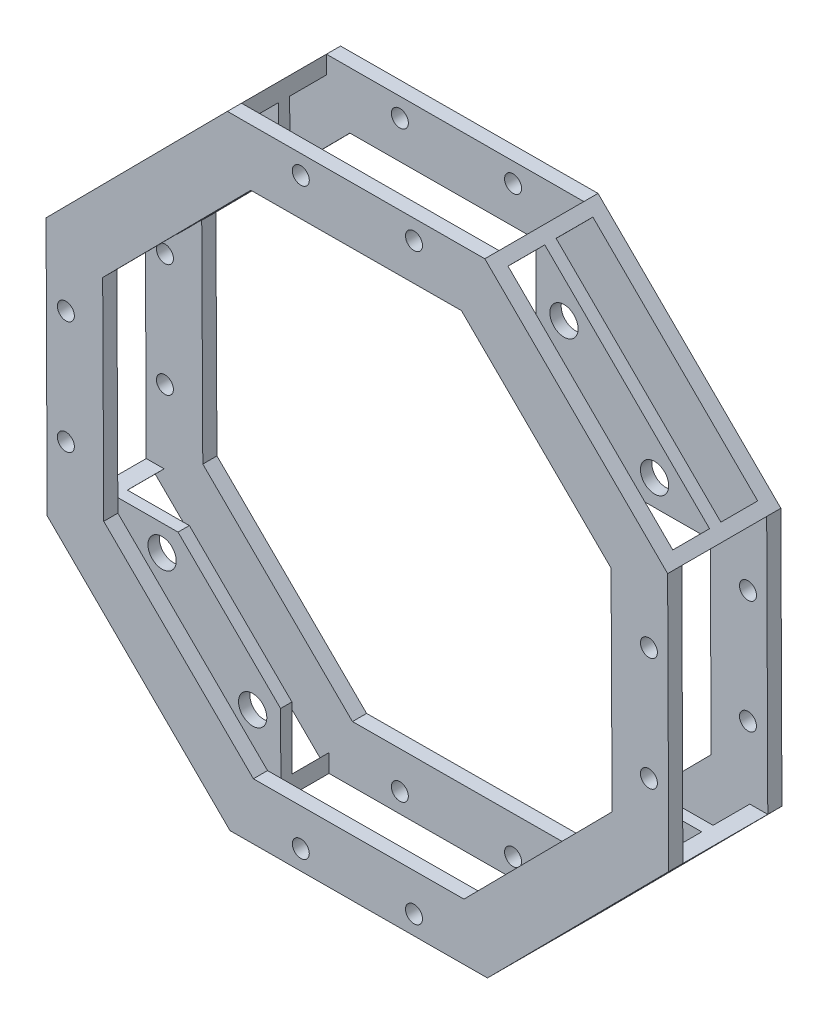
SolidWorks part; units mm, degrees
ref_plane "Plano frontal" through (0, 0, 0) normal (0, 0, 1) x (1, 0, 0)
ref_plane "Plano superior" through (0, 0, 0) normal (0, 1, 0) x (1, 0, 0)
ref_plane "Plano direito" through (0, 0, 0) normal (1, 0, 0) x (0, 0, -1)
sketch "Esboço1" plane through (0, 0, 0) normal (0, 0, 1) x (1, 0, 0)
  line L1 (109.614, 45.9495) -> (45.0177, 110)
  line L2 (45.0177, 110) -> (-45.9495, 109.614)
  line L3 (-45.9495, 109.614) -> (-110, 45.0177)
  line L4 (-110, 45.0177) -> (-109.614, -45.9495)
  line L5 (-109.614, -45.9495) -> (-45.0177, -110)
  line L6 (-45.0177, -110) -> (45.9495, -109.614)
  line L7 (45.9495, -109.614) -> (110, -45.0177)
  line L8 (110, -45.0177) -> (109.614, 45.9495)
  line L9 (89.6222, 37.657) -> (36.7449, 90)
  line L10 (36.7449, 90) -> (-37.657, 89.6222)
  line L11 (-37.657, 89.6222) -> (-90, 36.7449)
  line L12 (-90, 36.7449) -> (-89.6222, -37.657)
  line L13 (-89.6222, -37.657) -> (-36.7449, -90)
  line L14 (-36.7449, -90) -> (37.657, -89.6222)
  line L15 (37.657, -89.6222) -> (90, -36.7449)
  line L16 (90, -36.7449) -> (89.6222, 37.657)
  circle A0 centre (0, 0) radius 109.808 construction
  circle A1 centre (0, 0) radius 89.8123 construction
extrude "Ressalto-extrusão1" add sketch "Esboço1" along normal blind 40
sketch "Esboço2" plane through (109.807, 0.4659, 0) normal (1, 0.0042, 0) x (0, 0, -1)
  line L0 (-40, -45.484) -> (-40, 45.484) construction
  line L2 (0, 0) -> (0, -30)
  line L3 (0, -30) -> (-40, -30)
  line L4 (-40, 0) -> (-40, -30)
  line L5 (-40, -45.484) -> (0, -45.484) construction
  line L7 (0, 0) -> (0, -30)
  line L8 (0, -30) -> (-40, -30)
  line L9 (-40, 0) -> (-40, -30)
  line L10 (0, 45.484) -> (-5, 45.484)
  line L11 (0, 45.484) -> (0, -30)
  line L12 (0, -30) -> (-5, -30)
  line L13 (-5, 45.484) -> (-5, -30)
  line L14 (-40, 45.484) -> (-35, 45.484)
  line L15 (-40, 45.484) -> (-40, -30)
  line L16 (-40, -30) -> (-35, -30)
  line L17 (-35, 45.484) -> (-35, -30)
  line L18 (-5, -30) -> (-35, -30)
  line L19 (-5, -30) -> (-5, -45.484)
  line L20 (-5, -45.484) -> (-35, -45.484)
  line L21 (-35, -30) -> (-35, -45.484)
  point P23 (-3.1004, -30)
  line M2 (0, 45.484) -> (-40, 45.484)
  line M4 (-40, -45.484) -> (0, -45.484)
extrude "Corte-extrusão1" cut sketch "Esboço2" against normal through all both and the other way through all contours L17 L3 L13 M2 | L8 L21 L19 M4 region at (109.9672, -37.2757, 20) region at (109.7742, 8.2078, 20)
sketch "Esboço3" plane through (-0.4659, 109.807, 0) normal (-0.0042, 1, 0) x (1, 0.0042, 0)
  line L0 (45.484, -40) -> (-45.484, -40) construction
  line L1 (0, 0) -> (30, 0)
  line L3 (0, -40) -> (30, -40)
  line L4 (30, 0) -> (30, -40)
  line L5 (45.484, -40) -> (45.484, 0) construction
  line L6 (0, 0) -> (30.0922, 0)
  line L8 (0, -40) -> (30.0922, -40)
  line L9 (30.0922, 0) -> (30.0922, -5)
  line L10 (-45.484, 0) -> (30.0922, 0)
  line L11 (-45.484, 0) -> (-45.484, -5)
  line L12 (-45.484, -5) -> (30.0922, -5)
  line L13 (30.0922, 0) -> (30.0922, -5)
  line L14 (-45.484, -40) -> (30.0922, -40)
  line L15 (-45.484, -40) -> (-45.484, -35)
  line L16 (-45.484, -35) -> (30.0922, -35)
  line L17 (30.0922, -40) -> (30.0922, -35)
  line L18 (30, -35) -> (45.484, -35)
  line L19 (30, -35) -> (30, -5)
  line L20 (30, -5) -> (45.484, -5)
  line L21 (45.484, -35) -> (45.484, -5)
  line L22 (30.0922, -35) -> (30.0922, -40)
  line M2 (-45.484, 0) -> (-45.484, -40)
  line M4 (45.484, -40) -> (45.484, 0)
extrude "Corte-extrusão2" cut sketch "Esboço3" against normal through all both and the other way through all contours L20 L4 L18 M4 | L16 L9 L12 M2 region at (37.2757, 109.9672, 20) region at (-8.2078, 109.7742, 20)
sketch "Esboço4" plane through (77.3159, 77.9747, 0) normal (0.7041, 0.7101, 0) x (0, 0, -1)
  line L0 (-35, -45.484) -> (-5, -45.484) construction
  line L1 (-35, 45.484) -> (-5, 45.484)
  line L2 (-35, 45.484) -> (-35, -45.484)
  line L3 (-35, -45.484) -> (-5, -45.484)
  line L4 (-5, 45.484) -> (-5, -45.484)
  line L6 (-35, -45.484) -> (-5, -45.484)
  line L7 (-35, -45.484) -> (-35, -41)
  line L8 (-35, -41) -> (-5, -41)
  line L9 (-5, -45.484) -> (-5, -41)
  line L10 (-35, 45.484) -> (-5, 45.484)
  line L11 (-35, 45.484) -> (-35, 41)
  line L12 (-35, 41) -> (-5, 41)
  line L13 (-5, 45.484) -> (-5, 41)
  line L14 (-20, 41) -> (-18, 41)
  line L16 (-20, -41) -> (-18, -41)
  line L17 (-18, 41) -> (-18, -41)
  line L18 (-20, -41) -> (-22, -41)
  line L20 (-20, 41) -> (-22, 41)
  line L21 (-22, -41) -> (-22, 41)
extrude "Corte-extrusão3" cut sketch "Esboço4" against normal through all both and the other way through all contours L12 L17 L8 L4 | L8 L21 L12 L2 region at (77.3159, 77.9747, 28.5) region at (77.3159, 77.9747, 11.5)
sketch "Esboço5" plane through (-77.9747, 77.3159, 0) normal (-0.7101, 0.7041, 0) x (0, 0, 1)
  line L1 (35, 45.484) -> (5, 45.484)
  line L2 (35, 45.484) -> (35, -45.484)
  line L3 (35, -45.484) -> (5, -45.484)
  line L4 (5, 45.484) -> (5, -45.484)
  line L5 (5, -45.484) -> (35, -45.484)
  line L6 (5, -45.484) -> (5, -41)
  line L7 (5, -41) -> (35, -41)
  line L8 (35, -45.484) -> (35, -41)
  line L9 (5, 45.484) -> (35, 45.484)
  line L10 (5, 45.484) -> (5, 41)
  line L11 (5, 41) -> (35, 41)
  line L12 (35, 45.484) -> (35, 41)
  line L13 (20, 41) -> (22, 41)
  line L14 (20, 41) -> (20, -41)
  line L15 (20, -41) -> (22, -41)
  line L16 (22, 41) -> (22, -41)
  line L17 (20, 41) -> (18, 41)
  line L18 (20, 41) -> (20, -41)
  line L19 (20, -41) -> (18, -41)
  line L20 (18, 41) -> (18, -41)
extrude "Corte-extrusão4" cut sketch "Esboço5" against normal through all both and the other way through all contours L11 L16 L7 L2 | L20 L11 L4 L7 region at (-77.9747, 77.3159, 28.5) region at (-77.9747, 77.3159, 11.5)
sketch "Esboço6" plane through (0, 0, 18) normal (0, 0, -1) x (-1, 0, 0)
  circle A0 centre (-87, -55) radius 5
  circle A1 centre (-55, -87) radius 5
  circle A2 centre (55, 87) radius 5
  circle A3 centre (87, 55) radius 5
  circle A4 centre (-55, 87) radius 5
  circle A5 centre (-87, 55) radius 5
  circle A6 centre (87, -55) radius 5
  circle A7 centre (55, -87) radius 5
sketch "Esboço7" plane through (0, 0, 5) normal (0, 0, 1) x (1, 0, 0)
  circle A0 centre (-20, 103) radius 3
  circle A1 centre (20, 103) radius 3
  circle A2 centre (-20, -103) radius 3
  circle A3 centre (20, -103) radius 3
  circle A4 centre (-103, 20) radius 3
  circle A5 centre (-103, -20) radius 3
  circle A6 centre (103, 20) radius 3
  circle A7 centre (103, -20) radius 3
extrude "Corte-extrusão6" cut sketch "Esboço7" against normal through all both and the other way through all
extrude "Corte-extrusão5" cut sketch "Esboço6" against normal blind 10
